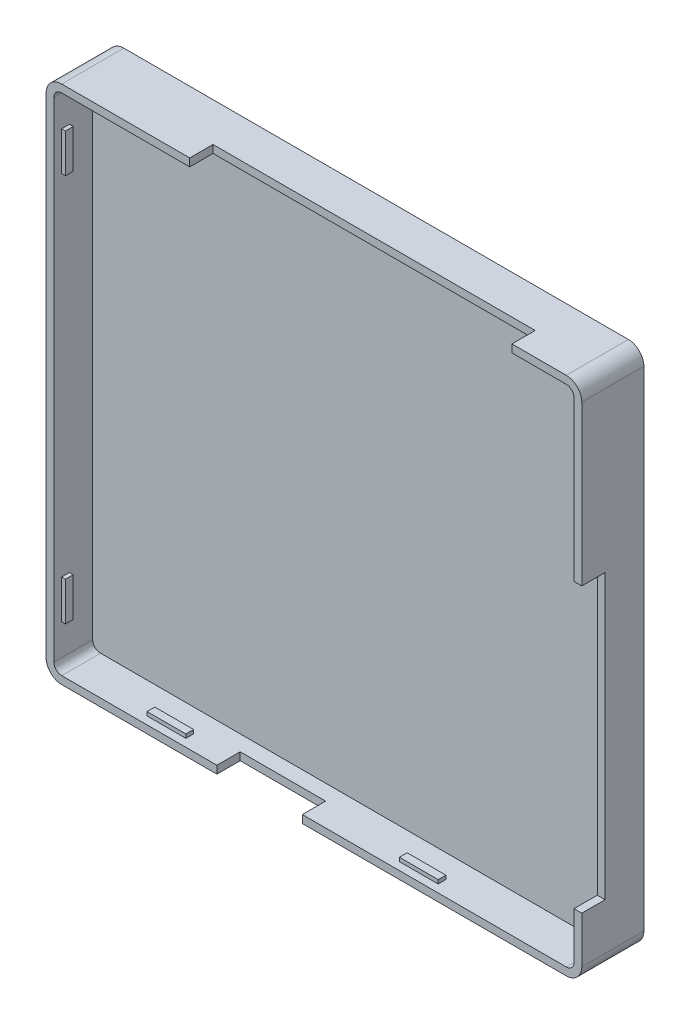
SolidWorks part; units mm, degrees
ref_plane "Plan de face" through (0, 0, 0) normal (0, 0, 1) x (1, 0, 0)
ref_plane "Plan de dessus" through (0, 0, 0) normal (0, 1, 0) x (1, 0, 0)
ref_plane "Plan de droite" through (0, 0, 0) normal (1, 0, 0) x (0, 0, -1)
sketch "Esquisse1" plane through (0, 0, 0) normal (0, 0, 1) x (1, 0, 0)
  line L1 (2, 0) -> (67, 0)
  line L2 (0, 2) -> (0, 65)
  line L3 (2, 67) -> (67, 67)
  line L4 (69, 2) -> (69, 65)
  arc A0 (2, 0) -> (0, 2) centre (2, 2) cw
  arc A1 (67, 0) -> (69, 2) centre (67, 2) ccw
  arc A2 (67, 67) -> (69, 65) centre (67, 65) cw
  arc A3 (0, 65) -> (2, 67) centre (2, 65) cw
  point P7 (0, 0)
  point P10 (69, 0)
  point P15 (0, 67)
  dimension "D3" = 2
  dimension "D1" = 67
  dimension "D2" = 69
extrude "Boss.-Extru.1" add sketch "Esquisse1" along normal blind 8
sketch "Esquisse3" plane through (0, 0, 8) normal (0, 0, 1) x (1, 0, 0)
  line L8 (2, 1) -> (67, 1)
  line L9 (68, 2) -> (68, 65)
  line L10 (67, 66) -> (2, 66)
  line L11 (1, 65) -> (1, 2)
  line L12 (2, 1) -> (67, 1)
  line L13 (68, 2) -> (68, 65)
  line L14 (67, 66) -> (2, 66)
  line L15 (1, 65) -> (1, 2)
  arc A8 (1, 2) -> (2, 1) centre (2, 2) ccw
  arc A9 (67, 1) -> (68, 2) centre (67, 2) ccw
  arc A10 (68, 65) -> (67, 66) centre (67, 65) ccw
  arc A11 (2, 66) -> (1, 65) centre (2, 65) ccw
  arc A12 (1, 2) -> (2, 1) centre (2, 2) ccw
  arc A13 (67, 1) -> (68, 2) centre (67, 2) ccw
  arc A14 (68, 65) -> (67, 66) centre (67, 65) ccw
  arc A15 (2, 66) -> (1, 65) centre (2, 65) ccw
  dimension "D1" = 1
extrude "Enlèv. mat.-Extru.1" cut sketch "Esquisse3" against normal blind 5
sketch "Esquisse4" plane through (0, 66, 0) normal (0, -1, 0) x (1, 0, 0)
  line L0 (67, 3) -> (2, 3) construction
  line L1 (8.1797, 6) -> (13.1797, 6)
  line L2 (8.1797, 6) -> (8.1797, 7)
  line L3 (8.1797, 7) -> (13.1797, 7)
  line L4 (13.1797, 6) -> (13.1797, 7)
  dimension "D1" = 3
  dimension "D2" = 1
  dimension "D3" = 5
extrude "Boss.-Extru.3" add sketch "Esquisse4" along normal blind 0.489 contours L1 L4 L3 L2
sketch "Esquisse5" plane through (68, 0, 0) normal (-1, 0, 0) x (0, 0, 1)
  line L0 (3, 2) -> (3, 65) construction
  line L1 (6, 62) -> (7, 62)
  line L2 (6, 62) -> (6, 57)
  line L3 (6, 57) -> (7, 57)
  line L4 (7, 62) -> (7, 57)
  line L5 (3, 65) -> (8, 65) construction
  dimension "D1" = 1
  dimension "D2" = 5
  dimension "D3" = 3
  dimension "D4" = 3
extrude "Boss.-Extru.4" add sketch "Esquisse5" along normal blind 0.489
sketch "Esquisse6" plane through (1, 0, 0) normal (1, 0, 0) x (0, 0, -1)
  line L0 (-3, 65) -> (-8, 65) construction
  line L1 (-6, 61) -> (-7, 61)
  line L2 (-6, 61) -> (-6, 56)
  line L3 (-6, 56) -> (-7, 56)
  line L4 (-7, 61) -> (-7, 56)
  line L5 (-3, 65) -> (-3, 2) construction
  dimension "D1" = 1
  dimension "D2" = 5
  dimension "D3" = 4
  dimension "D4" = 3
extrude "Boss.-Extru.5" add sketch "Esquisse6" along normal blind 0.489
sketch "Esquisse7" plane through (1, 0, 0) normal (1, 0, 0) x (0, 0, -1)
  line L0 (-3, 65) -> (-3, 2) construction
  line L1 (-6, 6) -> (-7, 6)
  line L2 (-6, 6) -> (-6, 11)
  line L3 (-6, 11) -> (-7, 11)
  line L4 (-7, 6) -> (-7, 11)
  line L5 (-3, 2) -> (-8, 2) construction
  point P4 (-1.4771, 9.3396)
  dimension "D1" = 5
  dimension "D2" = 1
  dimension "D3" = 3
  dimension "D4" = 4
extrude "Boss.-Extru.6" add sketch "Esquisse7" along normal blind 0.489
sketch "Esquisse8" plane through (0, 1, 0) normal (0, 1, 0) x (1, 0, 0)
  line L0 (2, -3) -> (67, -3) construction
  line L1 (12, -6) -> (17, -6)
  line L2 (12, -6) -> (12, -7)
  line L3 (12, -7) -> (17, -7)
  line L4 (17, -6) -> (17, -7)
  line L5 (2, -3) -> (2, -8) construction
  point P6 (12, -6.5)
  dimension "D1" = 1
  dimension "D2" = 5
  dimension "D3" = 3
  dimension "D4" = 10
extrude "Boss.-Extru.7" add sketch "Esquisse8" along normal blind 0.489
sketch "Esquisse9" plane through (0, 1, 0) normal (0, 1, 0) x (1, 0, 0)
  line L0 (2, -3) -> (67, -3) construction
  line L1 (49.5, -6) -> (44.5, -6)
  line L2 (49.5, -6) -> (49.5, -7)
  line L3 (49.5, -7) -> (44.5, -7)
  line L4 (44.5, -6) -> (44.5, -7)
  line L5 (67, -3) -> (67, -8) construction
  dimension "D1" = 5
  dimension "D2" = 1
  dimension "D3" = 3
  dimension "D4" = 17.5
extrude "Boss.-Extru.8" add sketch "Esquisse9" along normal blind 0.489
sketch "Esquisse10" plane through (68, 0, 0) normal (-1, 0, 0) x (0, 0, 1)
  line L0 (3, 2) -> (8, 2) construction
  line L1 (5, 8) -> (8, 8)
  line L2 (5, 8) -> (5, 44.5)
  line L3 (5, 44.5) -> (8, 44.5)
  line L4 (8, 8) -> (8, 44.5)
  line L5 (3, 2) -> (3, 65) construction
  dimension "D1" = 36.5
  dimension "D2" = 6
  dimension "D3" = 3
  dimension "D4" = 2
extrude "Enlèv. mat.-Extru.3" cut sketch "Esquisse10" against normal through all contours L2 L1 L4 L3
sketch "Esquisse11" plane through (0, 66, 0) normal (0, -1, 0) x (1, 0, 0)
  line L0 (67, 3) -> (67, 8) construction
  line L1 (60, 5) -> (18.5, 5)
  line L2 (60, 5) -> (60, 8)
  line L3 (60, 8) -> (18.5, 8)
  line L4 (18.5, 5) -> (18.5, 8)
  line L5 (67, 3) -> (2, 3) construction
  dimension "D1" = 7
  dimension "D2" = 41.5
  dimension "D3" = 3
  dimension "D4" = 2
extrude "Enlèv. mat.-Extru.4" cut sketch "Esquisse11" against normal through all
sketch "Esquisse12" plane through (0, 1, 0) normal (0, 1, 0) x (1, 0, 0)
  line L0 (2, -3) -> (2, -8) construction
  line L1 (22, -5) -> (33, -5)
  line L2 (22, -5) -> (22, -8)
  line L3 (22, -8) -> (33, -8)
  line L4 (33, -5) -> (33, -8)
  line L5 (2, -3) -> (67, -3) construction
  dimension "D1" = 11
  dimension "D2" = 20
  dimension "D3" = 3
  dimension "D4" = 2
extrude "Enlèv. mat.-Extru.5" cut sketch "Esquisse12" against normal through all
ref_plane "Plan3" through (2, 1, 3) normal (1, 0, 0) x (0, 0, -1)
